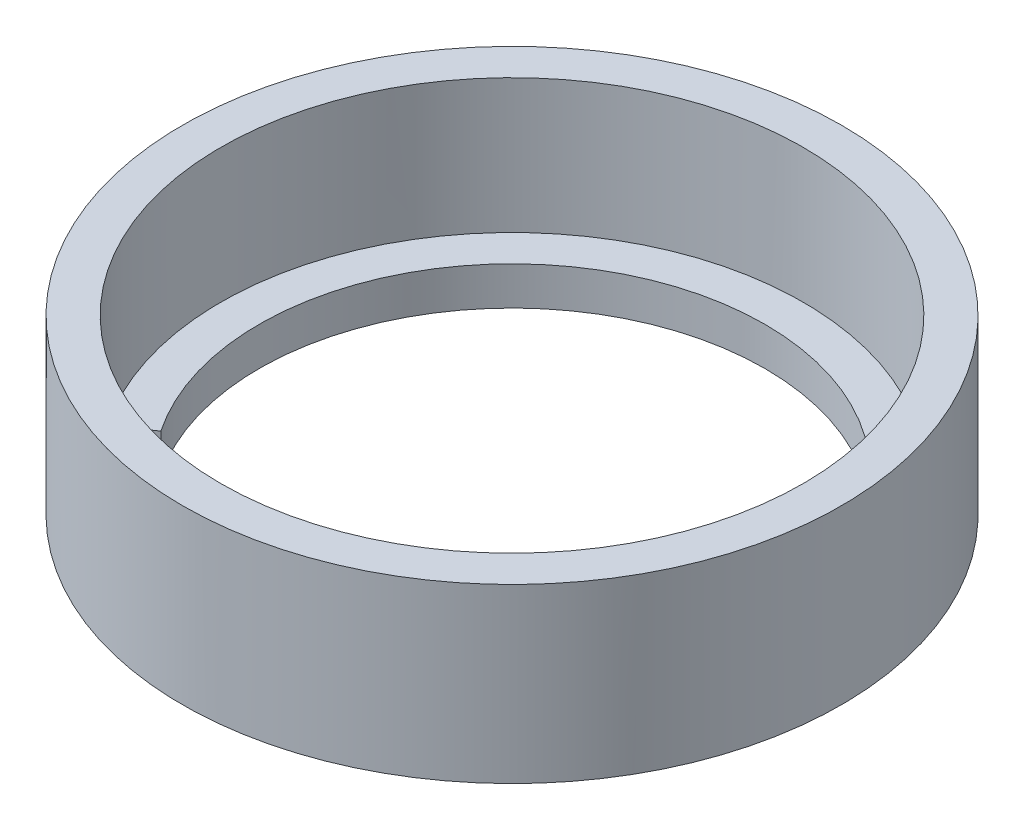
SolidWorks part; units mm, degrees
ref_plane "Front Plane" through (0, 0, 0) normal (0, 0, 1) x (1, 0, 0)
ref_plane "Top Plane" through (0, 0, 0) normal (0, 1, 0) x (1, 0, 0)
ref_plane "Right Plane" through (0, 0, 0) normal (1, 0, 0) x (0, 0, -1)
ref_axis "Axis1" through (0, -0.35, 0) along (0, 1, 0)
sketch "Sketch1" plane through (0, 0, 0) normal (0, 1, 0) x (1, 0, 0)
  circle A0 centre (0, 0) radius 15 construction
  circle A1 centre (0, 0) radius 15.2
  circle A2 centre (0, 0) radius 17.2
  dimension "D1" = 30
  dimension "D2" = 0.2
  dimension "D3" = 2
extrude "Boss-Extrude1" add sketch "Sketch1" along normal blind 7
sketch "Sketch2" plane through (0, 0, 0) normal (0, -1, 0) x (1, 0, 0)
  line L0 (0, 0) -> (0, 17.2) construction
  line L1 (0, 0) -> (-10.1099, 13.9151) construction
  line L2 (-10.9346, 7.3943) -> (-12.5913, 8.5146)
  line L3 (-3.6534, 12.6843) -> (-4.207, 14.6062)
  line L4 (-10.9346, 7.3943) -> (-7.294, 10.0393) construction
  line L5 (-7.294, 10.0393) -> (-3.6534, 12.6843) construction
  line L6 (3.6534, 12.6843) -> (4.207, 14.6062)
  line L7 (10.9346, 7.3943) -> (12.5913, 8.5146)
  line L8 (13.1925, 0.4451) -> (15.1914, 0.5125) [skipped]
  line L9 (10.4113, -8.1144) -> (11.9888, -9.3439) [skipped]
  line L10 (4.5, -12.4093) -> (5.1818, -14.2895) [skipped]
  line L11 (-4.5, -12.4093) -> (-5.1818, -14.2895) [skipped]
  line L12 (-10.4113, -8.1144) -> (-11.9888, -9.3439) [skipped]
  line L13 (-13.1925, 0.4451) -> (-15.1914, 0.5125) [skipped]
  circle A0 centre (0, 0) radius 17.2 construction
  circle A1 centre (0, 0) radius 15.2 construction
  circle A2 centre (0, 0) radius 15.2 construction
  circle A3 centre (0, 0) radius 17.2
  arc A4 (-10.9346, 7.3943) -> (10.9346, 7.3943) centre (0, 0) ccw
  arc A5 (-12.5913, 8.5146) -> (-4.207, 14.6062) centre (0, 0) cw
  arc A6 (4.207, 14.6062) -> (12.5913, 8.5146) centre (0, 0) cw
  arc A7 (15.1914, 0.5125) -> (11.9888, -9.3439) centre (0, 0) cw [skipped]
  arc A8 (5.1818, -14.2895) -> (-5.1818, -14.2895) centre (0, 0) cw [skipped]
  arc A9 (-11.9888, -9.3439) -> (-15.1914, 0.5125) centre (0, 0) cw [skipped]
  arc A10 (3.6534, 12.6843) -> (-3.6534, 12.6843) centre (0, 0) ccw
  point P35 (0, 0)
  dimension "D2" = 2
  dimension "D1" = 36
  dimension "D3" = 9
  dimension "D4" = 5
extrude "Boss-Extrude2" add sketch "Sketch2" along normal blind 2
